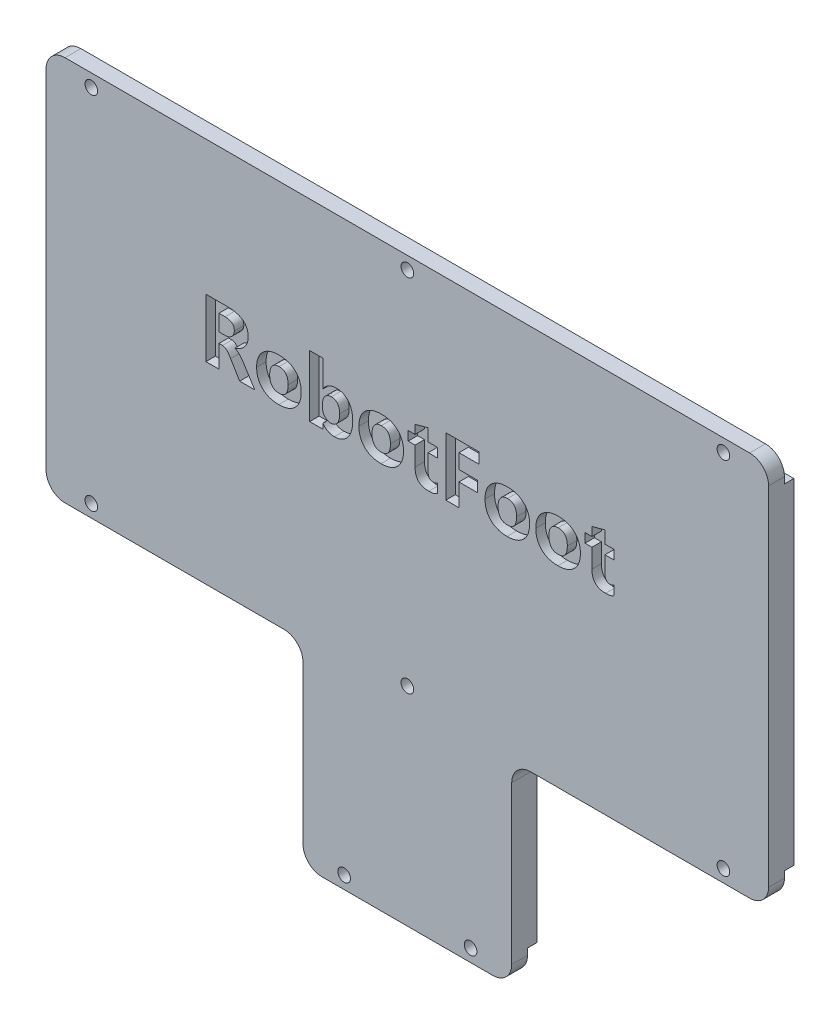
SolidWorks part; units mm, degrees
ref_plane "Plan de face" through (0, 0, 0) normal (0, 0, 1) x (1, 0, 0)
ref_plane "Plan de dessus" through (0, 0, 0) normal (0, 1, 0) x (1, 0, 0)
ref_plane "Plan de droite" through (0, 0, 0) normal (1, 0, 0) x (0, 0, -1)
sketch "Esquisse1" plane through (0, 0, 0) normal (0, 0, 1) x (1, 0, 0)
  line L0 (-57.15, 26.5) -> (57.15, 26.5)
  line L1 (-57.15, -30.5) -> (57.15, -30.5)
  line L2 (-57.15, -30.5) -> (-57.15, 30.5)
  line L3 (-57.15, 30.5) -> (57.15, 30.5)
  line L4 (57.15, -30.5) -> (57.15, 30.5)
  line L5 (-57.15, -30.5) -> (57.15, 30.5) construction
  line L6 (-57.15, 30.5) -> (57.15, -30.5) construction
  line L7 (-57.15, -26.5) -> (57.15, -26.5)
  line L8 (-16.51, -57.4) -> (16.51, -57.4)
  line L9 (-16.51, -30.5) -> (16.51, -30.5)
  line L10 (-16.51, -30.5) -> (-16.51, -61.4)
  line L11 (-16.51, -61.4) -> (16.51, -61.4)
  line L12 (16.51, -30.5) -> (16.51, -61.4)
  line L13 (57.15, 28.5) -> (-57.15, 28.5) construction
  line L14 (57.15, -28.5) -> (-57.15, -28.5) construction
  line L15 (16.51, -59.4) -> (-16.51, -59.4) construction
  circle A0 centre (50, 28.5) radius 1
  circle A1 centre (0, 28.5) radius 1
  circle A2 centre (-50, 28.5) radius 1
  circle A3 centre (50, -28.5) radius 1
  circle A4 centre (0, -28.5) radius 1
  circle A5 centre (-50, -28.5) radius 1
  circle A6 centre (10, -59.4) radius 1
  circle A7 centre (-10, -59.4) radius 1
  point P0 (0, 0)
  dimension "D11" = 3
  dimension "D13" = 7.15
  dimension "D15" = 2
  dimension "D1" = 114.3
  dimension "D2" = 61
  dimension "D3" = 30.9
  dimension "D4" = 33.02
  dimension "D5" = 4
  dimension "D6" = 4
  dimension "D7" = 2
  dimension "D8" = 2
  dimension "D9" = 4
  dimension "D10" = 2
  dimension "D12" = 7.15
  dimension "D16" = 6.51
  dimension "D14" = 3
extrude "Boss.-Extru.1" add sketch "Esquisse1" along normal blind 4 contours L1 L4 L3 L2 | L12 L1 L10 L11 | L2 L7 L4 L0 | L3 L4 L1 L2 | L11 L12 L9 L10 region at (-56.0063, 28.5, 0) region at (0, 0, 0) region at (0, -43.95, 0)
sketch "Esquisse2" plane through (0, 0, 4) normal (0, 0, 1) x (1, 0, 0)
  line L0 (-57.15, 0) -> (57.15, 0) construction
  line L1 (-57.15, -30.5) -> (-57.15, 30.5) construction
  line L2 (57.15, -30.5) -> (57.15, 30.5) construction
  text T0 "RobotFoot" font "Gadugi" height in points 36
extrude "Enlèv. mat.-Extru.1" cut sketch "Esquisse2" against normal blind 1.5
fillet "Congé9" radius 3 8 edges at (-57.15, 30.5, 2) (57.15, 30.5, 2) (57.15, -30.5, 2) (-57.15, -30.5, 2) (16.51, -61.4, 2) (-16.51, -61.4, 2)
extrude "Enlèv. mat.-Extru.8" cut sketch "Esquisse1<9>" along normal up to next contours A2 | A1 | A0 | A3 | A4 | A5 | A7 | A6
sketch "Esquisse1<9>" plane through (0, 0, 0) normal (0, 0, 1) x (1, 0, 0) same geometry as "Esquisse1"
extrude "Enlèv. mat.-Extru.10" cut sketch "Esquisse1<10>" along normal blind 1.5 contours L7 L2 L1 L4 A5 A4 A3 | L12 L8 L10 L11 A7 A6 | L0 L4 L3 L2 A2 A1 A0 region at (-56.0063, 28.5, 0) region at (0, -26.6144, 0) region at (0, -59.4, 0)
sketch "Esquisse1<10>" plane through (0, 0, 0) normal (0, 0, 1) x (1, 0, 0) same geometry as "Esquisse1"
